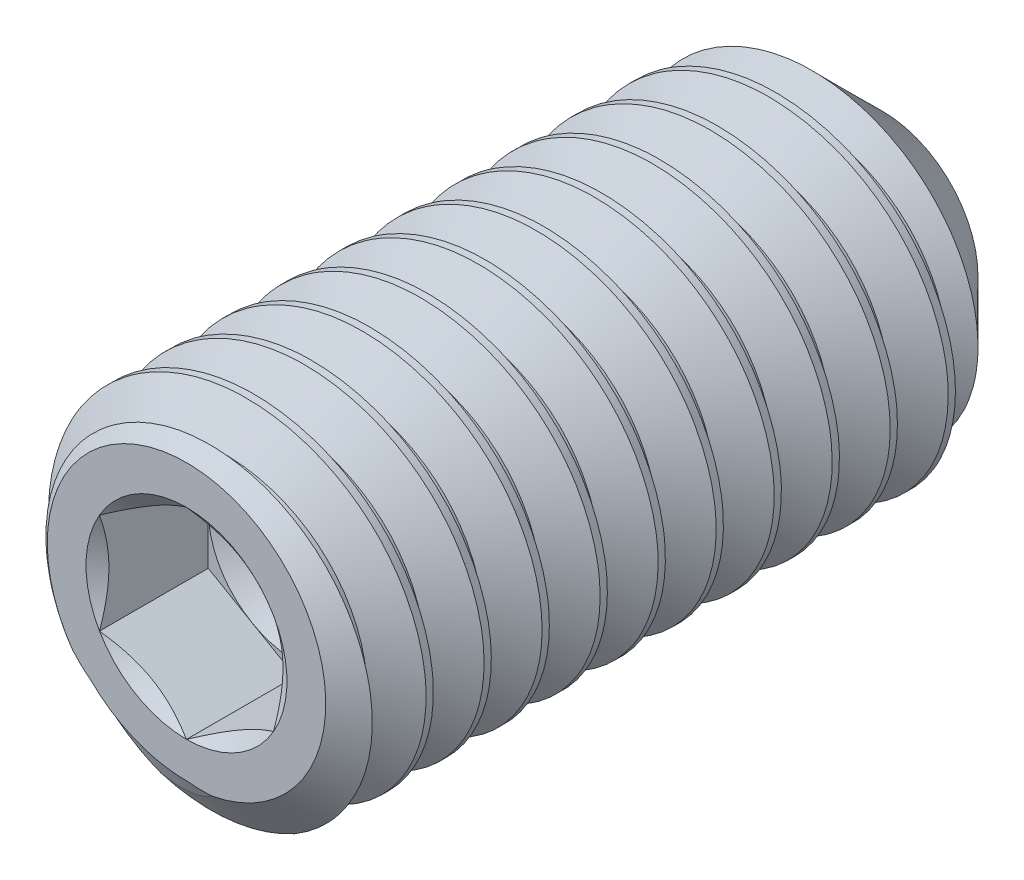
SolidWorks part; units mm, degrees
ref_plane "Front" through (0, 0, 0) normal (0, 0, 1) x (1, 0, 0)
ref_plane "Top" through (0, 0, 0) normal (0, 1, 0) x (1, 0, 0)
ref_plane "Right" through (0, 0, 0) normal (1, 0, 0) x (0, 0, -1)
sketch "Body Sketch" plane through (0, 0, 0) normal (1, 0, 0) x (0, 0, -1)
  line L0 (-2.7531, 0) -> (-2.7531, 1.2)
  line L1 (-2.7531, 1.2) -> (-2.543, 1.5)
  line L2 (-2.543, 1.5) -> (2.5689, 1.5)
  line L3 (2.5689, 1.5) -> (3.2469, 0.8219)
  line L4 (0.0129, 1.5) -> (0.0129, -1.5) construction
  line L5 (2.7531, 0) -> (-2.7531, 0)
  line L6 (-2.7531, 1.2) -> (-2.7531, -1.2) construction
  line L7 (2.7531, 0) -> (3.2469, 0.8219)
  line L8 (2.7531, 0) -> (3.2469, -0.8219) construction
  line L10 (2.7531, 0) -> (3.2469, 0) construction
  line L11 (3.2469, 0.8219) -> (3.2469, 0) construction
  point P11 (0.0129, 0)
  dimension "Length" = 6
  dimension "Top Chamfer" = 35
  dimension "Diameter" = 3
  dimension "D1" = 2.4
  dimension "D2" = 118
  dimension "D3" = 45
revolve "Body Revolve" add sketch "Body Sketch" angle 360 about L5
ref_plane "Bottom of Tip Plane" through (0, 0, -3.2469) normal (0, 0, 1) x (1, 0, 0)
sketch "Spiral Sketch" plane through (0, 0, -3.2469) normal (0, 0, 1) x (1, 0, 0)
  circle A0 centre (0, 0) radius 1.5 construction
  circle A1 centre (0, 0) radius 1.5
curve "Helix/Spiral" pitch 0.5 height 6.5 radius 1.5 centre (0, 0, -3.2469) axis (0, 0, 1) start towards (0, 1, 0) parameters "Thread Pitch"=0.5
sketch "Cut Sweep Sketch" plane through (0, 0, 0) normal (1, 0, 0) x (0, 0, -1)
  line L0 (3.2469, 1.5) -> (3.6844, 1.5)
  line L1 (3.6844, 1.5) -> (3.4969, 1.1752)
  line L2 (3.4969, 1.1752) -> (3.4344, 1.1752)
  line L3 (3.4344, 1.1752) -> (3.2469, 1.5)
  line L4 (3.3407, 1.3376) -> (3.5907, 1.3376) construction
  line L6 (-2.543, 1.5) -> (2.5689, 1.5) construction
  dimension "D1" = 0.0625
  dimension "D3" = 60
  dimension "D2" = 0.25
sweep "Cut Sweep" cut profiles "Cut Sweep Sketch" path "Helix/Spiral" align with end faces yes
sketch "Hex Sketch" plane through (0, 0, 2.7531) normal (0, 0, 1) x (1, 0, 0)
  line L1 (0, 0.866) -> (-0.75, 0.433)
  line L2 (-0.75, 0.433) -> (-0.75, -0.433)
  line L3 (-0.75, -0.433) -> (0, -0.866)
  line L4 (0, -0.866) -> (0.75, -0.433)
  line L5 (0.75, -0.433) -> (0.75, 0.433)
  line L6 (0.75, 0.433) -> (0, 0.866)
  circle A0 centre (0, 0) radius 0.75 construction
  dimension "Hex" = 1.5
extrude "Hex Extrude" cut sketch "Hex Sketch" against normal blind 0.9375
sketch "Hex Entry Sketch" plane through (0, 0, 2.7531) normal (0, 0, 1) x (1, 0, 0)
  circle A0 centre (0, 0) radius 0.866
extrude "Hex Entry Extrude" cut sketch "Hex Entry Sketch" against normal through all draft 55
sketch "Hex Bottom Sketch" plane through (0, 0, 1.8156) normal (0, 0, 1) x (1, 0, 0)
  circle A0 centre (0, 0) radius 0.75 construction
  circle A1 centre (0, 0) radius 0.75
extrude "Hex Bottom Extrude" cut sketch "Hex Bottom Sketch" against normal through all draft 60
equation "\"D1@Cut Sweep Sketch\" = \"Thread Pitch@Helix/Spiral\" * .125"
equation "\"D2@Cut Sweep Sketch\" = \"Thread Pitch@Helix/Spiral\" * .5"
equation "\"D3@Helix/Spiral\" = \"Length@Body Sketch\" + \"Thread Pitch@Helix/Spiral\""
equation "\"hex Depth@Hex Extrude\" = \"Hex@Hex Sketch\" * .625"
equation "\"D1@Body Sketch\" = \"Diameter@Body Sketch\" * .8"
equation "\"Diameter\"= 3mm"
equation "\"Thread Pitch\"= 0.5mm"
equation "\"Hex Size\"= 1.5mm"
equation "\"Diameter@Body Sketch\"=\"Diameter\""
equation "\"Thread Pitch@Helix/Spiral\"=\"Thread Pitch\""
equation "\"Hex@Hex Sketch\"=\"Hex Size\""
